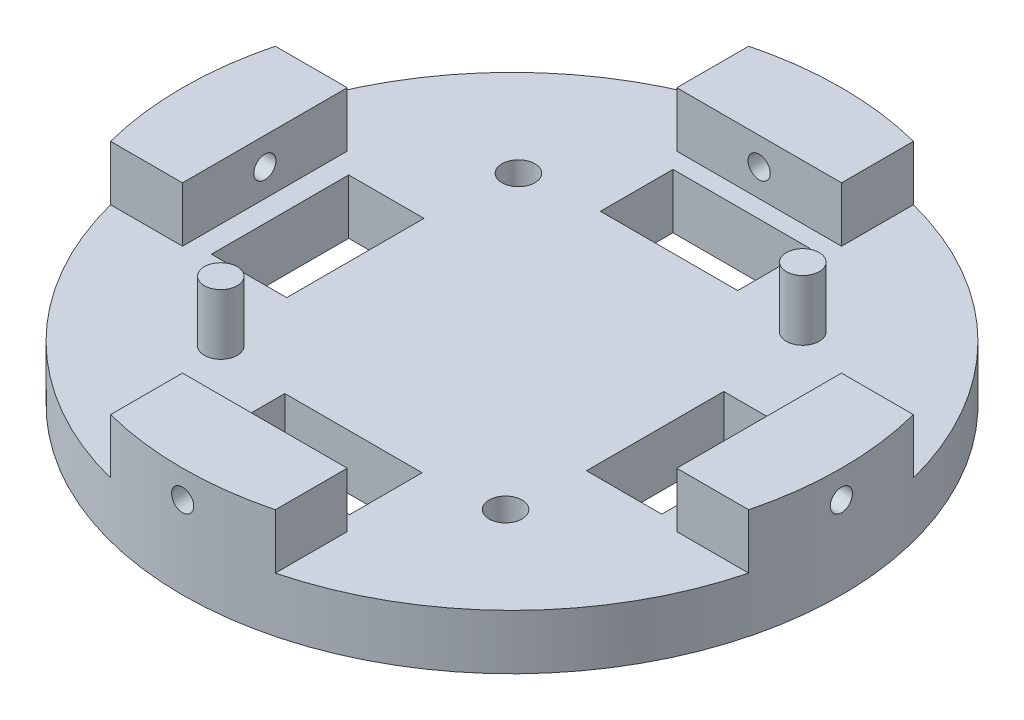
SolidWorks part; units mm, degrees
ref_plane "Front Plane" through (0, 0, 0) normal (0, 0, 1) x (1, 0, 0)
ref_plane "Top Plane" through (0, 0, 0) normal (0, 1, 0) x (1, 0, 0)
ref_plane "Right Plane" through (0, 0, 0) normal (1, 0, 0) x (0, 0, -1)
sketch "Sketch1" plane through (0, 0, 0) normal (0, 1, 0) x (1, 0, 0)
  circle A0 centre (0, 0) radius 76.2
  dimension "D1" = 152.4
extrude "Boss-Extrude1" add sketch "Sketch1" along normal blind 12.7
sketch "Sketch2" plane through (0, 12.7, 0) normal (0, 1, 0) x (1, 0, 0)
  line L9 (-19.05, -73.7803) -> (-19.05, -57.15)
  line L10 (-19.05, -57.15) -> (19.05, -57.15)
  line L11 (19.05, -57.15) -> (19.05, -73.7803)
  circle A0 centre (0, 0) radius 76.2 construction
  arc A1 (-19.05, -73.7803) -> (19.05, -73.7803) centre (0, 0) ccw
  point P20 (0, -57.15)
  point P22 (0, 0)
  point P23 (0, 0)
  point P24 (19.05, -73.7803)
  point P25 (19.05, -73.7803)
  point P26 (-19.05, -73.7803)
  dimension "D1" = 57.15
  dimension "D7" = 38.1
sketch "Sketch3" plane through (0, 12.7, 0) normal (0, 1, 0) x (1, 0, 0)
  point P0 (0, 0)
sketch "Sketch8" plane through (0, 12.7, 0) normal (0, 1, 0) x (1, 0, 0)
  arc A0 (-73.8992, 18.5835) -> (-73.6583, -19.5165) centre (0, 0) cw
  point P5 (0, 0)
sketch "Sketch9" plane through (0, 12.7, 0) normal (0, 1, 0) x (1, 0, 0)
  line L0 (34.52, 14.4543) -> (51.9245, 14.4543)
  line L1 (-52.2134, 14.4543) -> (-34.8089, 14.4543)
  line L2 (-52.2134, 14.4543) -> (-52.2134, -17.2957)
  line L3 (-52.2134, -17.2957) -> (-34.8089, -17.2957)
  line L4 (-34.8089, 14.4543) -> (-34.8089, -17.2957)
  line L5 (-15.8287, 53.0617) -> (15.9213, 53.0617)
  line L6 (-15.8287, 53.0617) -> (-15.8287, 36.2685)
  line L7 (-15.8287, 36.2685) -> (15.9213, 36.2685)
  line L8 (15.9213, 53.0617) -> (15.9213, 36.2685)
  line L9 (34.52, 14.4543) -> (34.52, -17.2957)
  line L10 (34.52, -17.2957) -> (51.9245, -17.2957)
  line L11 (51.9245, 14.4543) -> (51.9245, -17.2957)
  line L12 (-15.8287, -36.7093) -> (15.9213, -36.7093)
  line L13 (-15.8287, -36.7093) -> (-15.8287, -53.5025)
  line L14 (-15.8287, -53.5025) -> (15.9213, -53.5025)
  line L15 (15.9213, -36.7093) -> (15.9213, -53.5025)
  dimension "D1" = 31.75
  dimension "D2" = 31.75
extrude "Cut-Extrude1" cut sketch "Sketch9" against normal blind 12.7 contours L12 L15 L14 L13 | L0 L11 L10 L9 | L7 L8 L5 L6 | L1 L4 L3 L2
sketch "Sketch12" plane through (0, 12.7, 0) normal (0, 1, 0) x (1, 0, 0)
  circle A0 centre (-32.9232, 34.4123) radius 3.81
  circle A1 centre (32.9232, -34.4123) radius 3.81
  dimension "D1" = 7.62
  dimension "D2" = 95.25
  dimension "D3" = 180
  dimension "D4" = 47.625
extrude "Cut-Extrude7" cut sketch "Sketch12" against normal through all contours A1 | A0
sketch "Sketch14" plane through (0, 12.7, 0) normal (0, 1, 0) x (1, 0, 0)
  circle A0 centre (31.7143, 35.5295) radius 3.81
  circle A1 centre (-32.7613, -34.5809) radius 3.81
  dimension "D1" = 7.62
  dimension "D2" = 7.62
  dimension "D3" = 95.25
  dimension "D4" = 47.625
extrude "Boss-Extrude5" add sketch "Sketch14" along normal blind 13.97
extrude "Boss-Extrude6" add sketch "Sketch2" along normal blind 12.7 contours L10 L11 A1 L9
sketch "Sketch15" plane through (0, 0, 57.15) normal (0, 0, -1) x (-1, 0, 0)
  line L4 (-19.05, 25.4) -> (-19.05, 12.7) construction
  line L5 (19.05, 25.4) -> (-19.05, 25.4) construction
  circle A0 centre (0, 19.05) radius 2.5654
  point P2 (0, 0)
  point P6 (-19.05, 19.05)
  point P7 (0, 0)
  point P8 (0, 0)
  point P9 (0, 0)
  point P10 (0, 0)
  point P13 (0, 25.4)
  dimension "D1" = 5.1308
  dimension "D2" = 19.05
  dimension "D3" = 6.35
extrude "Cut-Extrude8" cut sketch "Sketch15" against normal through all
ref_axis "Axis1" through (0, 28.0035, 0) along (0, -1, 0)
pattern_circular "CirPattern1" count 4 over 360 about axis through (0, 28.0035, 0) along (0, -1, 0) of "Boss-Extrude6", "Cut-Extrude8"
equation "\"D2@Sketch15\"=1.5/2"
equation "\"D3@Sketch15\"=0.5/2"
